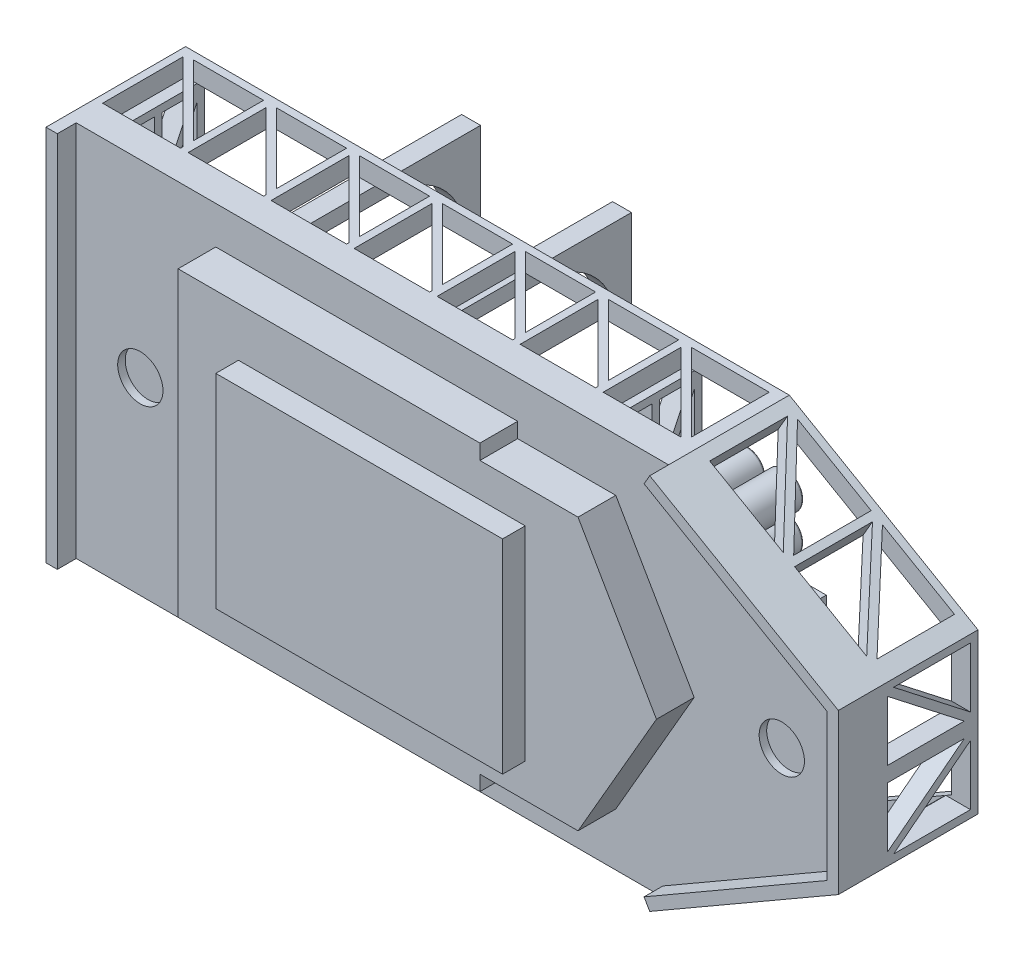
SolidWorks part; units mm, degrees
ref_plane "Front Plane" through (0, 0, 0) normal (0, 0, 1) x (1, 0, 0)
ref_plane "Top Plane" through (0, 0, 0) normal (0, 1, 0) x (1, 0, 0)
ref_plane "Right Plane" through (0, 0, 0) normal (1, 0, 0) x (0, 0, -1)
sketch "Sketch1" plane through (0, 0, 0) normal (0, 0, 1) x (1, 0, 0)
  line L0 (0, 0) -> (65, 0) construction
  line L1 (-40, -25) -> (40, -25)
  line L2 (-40, -25) -> (-40, 25)
  line L3 (-40, 25) -> (40, 25)
  line L5 (-40, -25) -> (40, 25) construction
  line L6 (-40, 25) -> (40, -25) construction
  line L7 (65, -10.5662) -> (65, 10.5662)
  line L9 (40, -25) -> (65, -10.5662)
  line L10 (40, 25) -> (65, 10.5662)
  point P0 (0, 0)
  dimension "D1" = 50
  dimension "D2" = 80
  dimension "D3" = 30
  dimension "D4" = 21.1325
extrude "Boss-Extrude1" add sketch "Sketch1" against normal blind 2
sketch "Sketch2" plane through (0, 0, -2) normal (0, 0, -1) x (-1, 0, 0)
  line L0 (40, 25) -> (40, -25) construction
  line L2 (37.5, 22.5) -> (-39.3301, 22.5)
  line L3 (-39.3301, 22.5) -> (-62.5, 9.1229)
  line L4 (-62.5, 9.1229) -> (-62.5, 0)
  line L7 (-40, 25) -> (40, 25) construction
  line L9 (-65, 10.5662) -> (-40, 25) construction
  line L10 (-65, -10.5662) -> (-65, 10.5662) construction
  line L11 (-62.5, 0) -> (-65, 0)
  line L12 (37.5, 22.5) -> (40, 22.5)
  line L13 (-65, 0) -> (-65, 10.5662)
  line L14 (40, 25) -> (40, 22.5)
  line L15 (-40, 25) -> (40, 25)
  line L16 (-65, 10.5662) -> (-40, 25)
  dimension "D2" = 2.5
  dimension "D3" = 2.5
  dimension "D4" = 2.5
extrude "Boss-Extrude2" add sketch "Sketch2" along normal blind 13
sketch "Sketch3" plane through (0, 22.5, 0) normal (0, -1, 0) x (1, 0, 0)
  line L0 (38.3301, -14) -> (28.0372, -14)
  line L1 (39.3301, -15) -> (39.3301, -2) construction
  line L2 (-40, -15) -> (-40, -2) construction
  line L3 (-39, -13.623) -> (-39, -3)
  line L4 (39.3301, -15) -> (-40, -15) construction
  line L5 (39.3301, -2) -> (-40, -2) construction
  line L6 (-39, -3) -> (-28.6699, -3)
  line L7 (38.3301, -3.7071) -> (38.3301, -14)
  line L8 (27.3301, -13.2929) -> (27.3301, -3)
  line L9 (26.3301, -14) -> (26.3301, -4.7071)
  line L10 (16.3301, -13.2929) -> (16.3301, -3)
  line L11 (15.3301, -14) -> (15.3301, -4.7071)
  line L12 (5.3301, -13.2929) -> (5.3301, -3)
  line L13 (4.3301, -14) -> (4.3301, -4.7071)
  line L14 (-5.6699, -13.2929) -> (-5.6699, -3)
  line L15 (-6.6699, -14) -> (-6.6699, -4.7071)
  line L16 (-16.6699, -13.2929) -> (-16.6699, -3)
  line L17 (-17.6699, -14) -> (-17.6699, -4.7071)
  line L18 (-27.6699, -13.2929) -> (-27.6699, -3)
  line L19 (-28.6699, -14) -> (-28.6699, -4.7071)
  line L20 (26.3301, -14) -> (17.0372, -14)
  line L21 (38.3301, -3.7071) -> (28.0372, -14)
  line L22 (37.623, -3) -> (27.3301, -13.2929)
  line L23 (26.3301, -4.7071) -> (17.0372, -14)
  line L24 (26.3301, -3.2929) -> (16.3301, -13.2929)
  line L25 (15.3301, -4.7071) -> (6.0372, -14)
  line L26 (15.3301, -3.2929) -> (5.3301, -13.2929)
  line L27 (4.3301, -4.7071) -> (-4.9628, -14)
  line L28 (4.3301, -3.2929) -> (-5.6699, -13.2929)
  line L29 (-6.6699, -4.7071) -> (-15.9628, -14)
  line L30 (-6.6699, -3.2929) -> (-16.6699, -13.2929)
  line L31 (-17.6699, -4.7071) -> (-26.9628, -14)
  line L32 (-17.6699, -3.2929) -> (-27.6699, -13.2929)
  line L33 (-28.6699, -4.7071) -> (-37.9628, -14)
  line L34 (-28.6699, -3.2929) -> (-38.6699, -13.2929)
  line L35 (-38.6699, -13.2929) -> (-39, -13.623)
  line L36 (27.3301, -3) -> (37.623, -3)
  line L37 (26.3301, -3.2929) -> (26.3301, -3)
  line L38 (15.3301, -14) -> (6.0372, -14)
  line L39 (16.3301, -3) -> (26.3301, -3)
  line L40 (15.3301, -3.2929) -> (15.3301, -3)
  line L41 (4.3301, -14) -> (-4.9628, -14)
  line L42 (5.3301, -3) -> (15.3301, -3)
  line L43 (4.3301, -3.2929) -> (4.3301, -3)
  line L44 (-6.6699, -14) -> (-15.9628, -14)
  line L45 (-5.6699, -3) -> (4.3301, -3)
  line L46 (-6.6699, -3.2929) -> (-6.6699, -3)
  line L47 (-17.6699, -14) -> (-26.9628, -14)
  line L48 (-16.6699, -3) -> (-6.6699, -3)
  line L49 (-17.6699, -3.2929) -> (-17.6699, -3)
  line L50 (-28.6699, -14) -> (-37.9628, -14)
  line L51 (-27.6699, -3) -> (-17.6699, -3)
  line L52 (-28.6699, -3.2929) -> (-28.6699, -3)
  dimension "D1" = 1
  dimension "D2" = 1
  dimension "D3" = 1
  dimension "D4" = 1
  dimension "D5" = 1
  dimension "D7" = 6
  dimension "D8" = 1
  dimension "D9" = 7
extrude "Cut-Extrude1" cut sketch "Sketch3" against normal blind 13
sketch "Sketch4" plane through (19.5753, 33.9054, 0) normal (-0.5, -0.866, 0) x (0.866, -0.5, 0)
  line L0 (23.8109, -3) -> (23.8109, -13.3217)
  line L1 (23.8109, -13.3217) -> (35.0709, -3)
  line L2 (49.5652, -15) -> (22.8109, -15) construction
  line L3 (24.5508, -14) -> (35.8109, -14)
  line L4 (22.8109, -15) -> (22.8109, -2) construction
  line L5 (49.5652, -15) -> (49.5652, -2) construction
  line L6 (48.5652, -14) -> (48.5652, -3.7301)
  line L7 (47.8334, -3) -> (36.8109, -3)
  line L8 (-22.141, -2) -> (47.141, -2) construction
  line L9 (35.8109, -3.7372) -> (35.8109, -14)
  line L10 (36.8109, -3) -> (36.8109, -13.3152)
  line L11 (35.0709, -3) -> (23.8109, -3)
  line L12 (37.5426, -14) -> (48.5652, -14)
  line L15 (24.5508, -14) -> (35.8109, -3.7372)
  line L16 (36.8109, -13.3152) -> (47.8334, -3)
  line L17 (37.5426, -14) -> (48.5652, -3.7301)
  dimension "D1" = 1
  dimension "D2" = 1
  dimension "D3" = 1
  dimension "D4" = 1
  dimension "D5" = 1
  dimension "D6" = 12
extrude "Cut-Extrude2" cut sketch "Sketch4" against normal blind 13
sketch "Sketch5" plane through (65, 0, 0) normal (1, 0, 0) x (0, 0, -1)
  line L0 (14, 9.5662) -> (3.8138, 9.5662)
  line L1 (15, 10.5662) -> (15, 0) construction
  line L3 (14, 9.5662) -> (14, 1.6337)
  line L4 (15, 10.5662) -> (0, 10.5662) construction
  line L5 (15, 0) -> (2, 0) construction
  line L6 (13.1862, 1) -> (3, 1)
  line L7 (3, 8.9325) -> (3, 1)
  line L9 (3.8138, 9.5662) -> (14, 1.6337)
  line L10 (3, 8.9325) -> (13.1862, 1)
  dimension "D1" = 1
  dimension "D2" = 1
  dimension "D3" = 1
  dimension "D4" = 1
extrude "Cut-Extrude3" cut sketch "Sketch5" against normal blind 13
mirror "Mirror1" about plane through (62.5, 0, -15) normal (0, 1, 0) of "Cut-Extrude3", "Cut-Extrude2", "Boss-Extrude2", "Cut-Extrude1"
sketch "Sketch6" plane through (0, 0, -2) normal (0, 0, -1) x (-1, 0, 0)
  line L0 (-28.4026, -22.5) -> (-28.4026, 22.5)
  line L1 (-39.3301, -22.5) -> (40, -22.5) construction
  line L2 (-39.3301, 22.5) -> (40, 22.5) construction
  line L3 (-25.9026, -22.5) -> (-25.9026, 22.5)
  line L4 (-28.4026, -22.5) -> (-25.9026, -22.5)
  line L5 (-28.4026, 22.5) -> (-25.9026, 22.5)
  dimension "D1" = 2.5
  dimension "D2" = 25.9026
extrude "Boss-Extrude3" add sketch "Sketch6" along normal blind 13
sketch "Sketch7" plane through (25.9026, 0, 0) normal (-1, 0, 0) x (0, 0, 1)
  line L0 (-14, -19.1763) -> (-14, -11.6371)
  line L1 (-8.375, -21.5) -> (-4.3039, -21.5)
  line L3 (-13.4461, 21.5) -> (-9.375, 21.5)
  line L4 (-15, -22.5) -> (-15, 22.5) construction
  line L6 (-3.75, 19.3787) -> (-3.75, 10.7886)
  line L7 (-15, 22.5) -> (-2, 22.5) construction
  line L9 (-14, -21.5) -> (-9.375, -21.5)
  line L10 (-14, -22.5) -> (-5.1346, -22.5) construction
  line L11 (-14, -11.6371) -> (-9.9702, -11.6371)
  line L12 (-2, -22.5) -> (-2, 22.5) construction
  line L15 (-8.876, 9.7886) -> (-8.875, 9.7886)
  line L19 (-14, -10.6371) -> (-9.4828, -10.6371)
  line L22 (-14, 9.7886) -> (-10.0099, 9.7886)
  line L23 (-14, 10.7886) -> (-9.4473, 10.7886)
  line L24 (-9.375, -21.5) -> (-9.375, -12.6449)
  line L25 (-8.375, -21.5) -> (-8.375, -12.9606)
  line L26 (-14.1082, -21.5) -> (-9.375, -12.6449)
  line L27 (-14, -19.1763) -> (-9.9702, -11.6371)
  line L28 (-14, 20.3381) -> (-9.4473, 10.7886)
  line L29 (-13.4461, 21.5) -> (-9.375, 12.9606)
  line L30 (-4.3039, -21.5) -> (-8.375, -12.9606)
  line L31 (-3.75, -20.3381) -> (-7.8982, -11.6371)
  line L32 (-3.75, 19.3787) -> (-8.3415, 10.7886)
  line L33 (-3.75, 21.5) -> (-8.375, 12.8473)
  line L37 (-14, -10.6371) -> (-14, -1.1619)
  line L38 (-3.75, -11.6371) -> (-3.75, -20.3381)
  line L39 (-8.3018, -10.6371) -> (-3.75, -2.1213)
  line L40 (-8.3018, -10.6371) -> (-3.75, -10.6371)
  line L41 (-3.75, -2.1213) -> (-3.75, -10.6371)
  line L43 (-9.4828, -10.6371) -> (-14, -1.1619)
  line L45 (-9.375, -8.5394) -> (-9.375, -0.5)
  line L46 (-9.375, -8.5394) -> (-13.2077, -0.5)
  line L47 (-8.375, -8.6527) -> (-4.0173, -0.5)
  line L48 (-8.375, -8.6527) -> (-8.375, -0.5)
  line L50 (-8.375, -0.5) -> (-4.0173, -0.5)
  line L51 (-8.375, 0.5) -> (-8.375, 8.5394)
  line L52 (-9.375, 0.5) -> (-9.375, 8.8551)
  line L53 (-13.2077, -0.5) -> (-9.375, -0.5)
  line L56 (-8.375, 0.5) -> (-4.5423, 0.5)
  line L57 (-13.8409, 0.5) -> (-9.375, 0.5)
  line L58 (-14, 2.3237) -> (-14, 9.7886)
  line L59 (-8.375, 8.5394) -> (-4.5423, 0.5)
  line L61 (-7.8627, 9.7886) -> (-3.75, 9.7886)
  line L62 (-7.8627, 9.7886) -> (-3.75, 1.1619)
  line L63 (-9.375, 8.8551) -> (-13.8409, 0.5)
  line L66 (-10.0099, 9.7886) -> (-14, 2.3237)
  line L67 (-14, 10.7886) -> (-14, 20.3381)
  line L68 (-3.75, 9.7886) -> (-3.75, 1.1619)
  line L69 (-9.375, 12.9606) -> (-9.375, 21.5)
  line L72 (-8.375, 12.8473) -> (-8.375, 21.5)
  line L73 (-8.375, 21.5) -> (-3.75, 21.5)
  line L78 (-8.3415, 10.7886) -> (-3.75, 10.7886)
  line L79 (-7.8982, -11.6371) -> (-3.75, -11.6371)
  line L81 (-8.375, -10.6371) -> (-8.375, -10.6369)
  line L83 (-14.1082, -21.5) -> (-14, -21.5)
  line L86 (-8.875, 9.7886) -> (-8.875, 9.7905) construction
  dimension "D1" = 1
  dimension "D2" = 1
  dimension "D3" = 1
  dimension "D4" = 1.75
  dimension "D5" = 1
  dimension "D6" = 1
  dimension "D7" = 1
  dimension "D9" = 1
  dimension "D10" = 1
  dimension "D11" = 1
  dimension "D12" = 1
extrude "Cut-Extrude4" cut sketch "Sketch7" against normal blind 6 contours L26 L83 L9 L24 | L0 L27 L11 | L19 L43 L37 | L53 L46 L45 | L50 L48 L47 | L59 L51 L56 | L52 L63 L57 | L67 L23 L28 | L29 L69 L3 | L73 L72 L33 | L32 L78 L6 | L68 L61 L62 | L41 L39 L40 | L79 L31 L38 | L1 L30 L25 | L58 L22 L66 region at (25.9026, -14.1501, -12.6567) region at (25.9026, -18.6535, -7.018) region at (25.9026, 18.6535, -10.732) region at (25.9026, 13.6519, -5.2805) region at (25.9026, -18.5483, -10.9527) region at (25.9026, -7.4787, -12.4943) region at (25.9026, 13.9718, -12.4824) region at (25.9026, -14.5374, -5.1327) region at (25.9026, 18.6158, -6.8333) region at (25.9026, -7.7985, -5.2673) region at (25.9026, -3.1798, -10.6526) region at (25.9026, -3.2176, -6.9224) region at (25.9026, 3.1798, -7.0974) region at (25.9026, 3.285, -10.8636) region at (25.9026, 6.913, -5.1209)
ref_plane "Plane1" through (-5.7974, 0, 0) normal (1, 0, 0) x (0, 0, -1)
mirror "Mirror2" about plane through (-5.7974, 0, 0) normal (1, 0, 0) of "Cut-Extrude4", "Boss-Extrude3"
sketch "Sketch8" plane through (-39.9974, 0, 0) normal (-1, 0, 0) x (0, 0, 1)
  line L0 (-15, -10.6371) -> (-2, -10.6371)
  line L1 (-15, 22.5) -> (-15, -22.5) construction
  line L2 (-2, 22.5) -> (-2, -22.5) construction
  line L3 (-2, -10.6371) -> (-2, 9.7886)
  line L4 (-2, 9.7886) -> (-15, 9.7886)
  line L5 (-15, 9.7886) -> (-15, -10.6371)
extrude "Cut-Extrude5" cut sketch "Sketch8" against normal blind 6
sketch "Sketch9" plane through (0, 0, -2) normal (0, 0, -1) x (-1, 0, 0)
  line L0 (-6.0795, 22.5) -> (-6.0795, 7.5)
  line L1 (-25.9026, 22.5) -> (37.4974, 22.5) construction
  line L2 (-6.0795, 7.5) -> (-3.5795, 7.5)
  line L3 (-3.5795, 7.5) -> (-3.5795, 22.5)
  line L4 (-6.0795, 22.5) -> (-3.5795, 22.5)
  dimension "D1" = 2.5
  dimension "D2" = 3.5795
  dimension "D3" = 15
extrude "Boss-Extrude4" add sketch "Sketch9" along normal blind 26
sketch "Sketch11" plane through (0, 0, 0) normal (0, 0, 1) x (1, 0, 0)
  line L7 (-40, -25) -> (40, -25)
  line L8 (40, -25) -> (65, -10.5662)
  line L9 (65, -10.5662) -> (65, 10.5662)
  line L10 (65, 10.5662) -> (40, 25)
  line L11 (40, 25) -> (-40, 25)
  line L12 (-40, 25) -> (-40, -25)
  line L13 (-40, -25) -> (40, -25)
  line L14 (40, -25) -> (65, -10.5662)
  line L15 (65, -10.5662) -> (65, 10.5662)
  line L16 (65, 10.5662) -> (40, 25)
  line L17 (40, 25) -> (-40, 25)
  line L18 (-40, 25) -> (-40, -25)
  circle A0 centre (55, 0) radius 3
  circle A1 centre (-30, 0) radius 3
  dimension "D1" = 6
  dimension "D2" = 55
  dimension "D3" = 30
  dimension "D4" = 0
extrude "Boss-Extrude6" add sketch "Sketch11" along normal blind 1
sketch "Sketch12" plane through (0, 0, 1) normal (0, 0, 1) x (1, 0, 0)
  line L1 (-20, -20) -> (20, -20)
  line L2 (-20, -20) -> (-20, 20)
  line L3 (-20, 20) -> (20, 20)
  line L4 (20, -20) -> (20, 20)
  line L5 (-20, -20) -> (20, 20) construction
  line L6 (-20, 20) -> (20, -20) construction
  point P0 (0, 0)
  dimension "D1" = 40
  dimension "D2" = 20
extrude "Boss-Extrude7" add sketch "Sketch12" along normal blind 5
sketch "Sketch13" plane through (0, 0, 1) normal (0, 0, 1) x (1, 0, 0)
  line L0 (20, 0) -> (43.7696, 0) construction
  line L1 (20, -20) -> (20, 20) construction
  line L2 (20, 18) -> (33, 18)
  line L3 (33, 18) -> (43.3923, 0)
  line L4 (33, -18) -> (43.3923, 0)
  line L5 (20, -18) -> (33, -18)
  line L6 (20, 18) -> (20, -18)
  dimension "D1" = 60
  dimension "D2" = 13
  dimension "D3" = 18
extrude "Boss-Extrude8" add sketch "Sketch13" along normal blind 5
sketch "Sketch14" plane through (0, 0, 6) normal (0, 0, 1) x (1, 0, 0)
  line L1 (-12, -13.4999) -> (26, -13.4999)
  line L2 (-12, -13.4999) -> (-12, 13.4999)
  line L3 (-12, 13.4999) -> (26, 13.4999)
  line L4 (26, -13.4999) -> (26, 13.4999)
  line L5 (-12, -13.4999) -> (26, 13.4999) construction
  line L6 (-12, 13.4999) -> (26, -13.4999) construction
  point P0 (7, 0)
  dimension "D1" = 7
  dimension "D2" = 26.9999
  dimension "D3" = 38
extrude "Boss-Extrude9" add sketch "Sketch14" along normal blind 3
sketch "Sketch15" plane through (0, 0, 1) normal (0, 0, 1) x (1, 0, 0)
  line L0 (-40, 25) -> (-40, -25) construction
  line L1 (40, -25) -> (65, -10.5662) construction
  line L2 (65, -10.5662) -> (65, 10.5662) construction
  line L3 (65, 10.5662) -> (40, 25) construction
  line L4 (-40, 25) -> (-40, -25)
  line L5 (40, -25) -> (65, -10.5662)
  line L6 (65, -10.5662) -> (65, 10.5662)
  line L7 (65, 10.5662) -> (40, 25)
  line L8 (-38.5, 25) -> (-38.5, -25)
  line L9 (39.25, -23.701) -> (63.5, -9.7002)
  line L10 (63.5, -9.7002) -> (63.5, 9.7002)
  line L11 (63.5, 9.7002) -> (39.25, 23.701)
  line L12 (-40, 25) -> (-38.5, 25)
  line L13 (-40, -25) -> (-38.5, -25)
  line L14 (39.25, -23.701) -> (40, -25)
  line L15 (40, 25) -> (39.25, 23.701)
  dimension "D1" = 1.5
extrude "Boss-Extrude10" add sketch "Sketch15" along normal blind 2.5
sketch "Sketch16" plane through (3.5795, 0, 0) normal (-1, 0, 0) x (0, 0, 1)
  line L0 (-2, 7.5) -> (-26, 7.5)
  line L1 (-28, 7.5) -> (-2, 7.5) construction
  line L3 (-16, 20.5) -> (-2, 20.5)
  line L4 (-2, 22.5) -> (-2, 9.7886) construction
  line L5 (-2, 20.5) -> (-2, 7.5)
  line L7 (-26, 10.5) -> (-28, 10.5)
  line L8 (-28, 7.5) -> (-28, 22.5) construction
  line L9 (-28, 10.5) -> (-28, 7.5)
  line L10 (-28, 7.5) -> (-26, 7.5)
  arc A0 (-26, 10.5) -> (-16, 20.5) centre (-16, 10.5) cw
  point P13 (-26, 20.5)
  dimension "D3" = 10
  dimension "D1" = 24
  dimension "D2" = 13
extrude "Cut-Extrude6" cut sketch "Sketch16" against normal blind 5
pattern_linear "LPattern1" count 2 spacing 20 along (-1, 0, 0) of "Cut-Extrude6", "Boss-Extrude4"
mirror "Mirror3" about plane through (0, 0, 0) normal (0, 1, 0) of "Boss-Extrude4", "LPattern1", "Cut-Extrude6"
sketch "Sketch17" plane through (0, 0, -2) normal (0, 0, -1) x (-1, 0, 0)
  line L0 (6.1995, 0) -> (-74.6011, 0) construction
  line L2 (-50.4, -10) -> (-40.6, -10)
  line L4 (-50.4, 10) -> (-40.6, 10)
  line L6 (-50.5, -10) -> (-40.5, 10) construction
  line L7 (-50.5, 10) -> (-40.5, -10) construction
  line L12 (-41, 10) -> (-41, 15.5)
  line L13 (-41, 15.5) -> (-30, 15.5)
  line L14 (-30, 15.5) -> (-30, -15.5)
  line L15 (-30, -15.5) -> (-41, -15.5)
  line L16 (-41, -15.5) -> (-41, -10)
  line L18 (-35.5, 15) -> (-35.5, -15) construction
  line L19 (-40.5, 10) -> (-40.6, 10)
  line L20 (-50.4, -9.9) -> (-50.4, 9.9)
  line L21 (-40.6, 10) -> (-40.6, -10)
  line L22 (-50.4, 9.9) -> (-50.4, 10)
  line L23 (-50.4, 9.9) -> (-40.5, 9.9) construction
  line L24 (-50.4, -9.9) -> (-50.4, -10)
  line L25 (-50.4, -9.9) -> (-40.5, -9.9) construction
  line L26 (-50.5, -10) -> (-50.5, 10) construction
  line L27 (-50.5, -10) -> (-40.5, -10) construction
  line L28 (-50.5, 10) -> (-40.5, 10) construction
  line L29 (-40.5, -10) -> (-40.6, -10)
  line L30 (-40.6, 10.1) -> (-40.6, 10.1)
  line L31 (-40.6, 10.1) -> (-40.6, 15.1)
  line L32 (-40.6, 15.1) -> (-30.4, 15.1)
  line L33 (-30.4, 15.1) -> (-30.4, -15.1)
  line L34 (-30.4, -15.1) -> (-40.6, -15.1)
  line L35 (-40.6, -15.1) -> (-40.6, -10.1)
  line L36 (-40.6, -10.1) -> (-40.6, -10.1)
  line L37 (-40.5, -15) -> (-40.5, -10) construction
  line L38 (-30.5, -15) -> (-40.5, -15) construction
  line L39 (-40.6, -10.1) -> (-40.6, -10)
  line L40 (-40.6, 10.1) -> (-40.6, 10)
  line L42 (-40.5, 10) -> (-40.5, 15) construction
  line L43 (-40.5, 15) -> (-30.5, 15) construction
  line L44 (-30.5, 15) -> (-30.5, -15) construction
  circle A0 centre (-55, 0) radius 4.5
  circle A13 centre (-33, 12.5) radius 2.4
  circle A14 centre (-33, 7.5) radius 2.4
  circle A15 centre (-33, 2.5) radius 2.4
  circle A16 centre (-33, -2.5) radius 2.4
  circle A17 centre (-33, -7.5) radius 2.4
  circle A18 centre (-33, -12.5) radius 2.4
  circle A20 centre (-38, 12.5) radius 2.4
  circle A21 centre (-38, 7.5) radius 2.4
  circle A22 centre (-38, 2.5) radius 2.4
  circle A23 centre (-38, -2.5) radius 2.4
  circle A24 centre (-38, -7.5) radius 2.4
  circle A25 centre (-38, -12.5) radius 2.4
  point P5 (-45.5, 0)
  dimension "D1" = 9
  dimension "D2" = 20
  dimension "D3" = 10
  dimension "D12" = 0.1
  dimension "D11" = 0.1
extrude "Boss-Extrude11" add sketch "Sketch17" along normal blind 5 contours A0 region at (55, 0, -2)
extrude "Boss-Extrude14" add sketch "Sketch17<4>" along normal blind 7.5 contours L20 L24 L2 L21 L4 L22 region at (45.5, 0, -2)
sketch "Sketch17<4>" plane through (0, 0, -2) normal (0, 0, -1) x (-1, 0, 0) same geometry as "Sketch17"
extrude "Boss-Extrude15" add sketch "Sketch17<5>" along normal blind 4.5 contours L40 L31 L32 L33 L34 L35 L39 L2 L16 L15 L14 L13 L12 L4 region at (40.8, -10.3289, -2)
sketch "Sketch17<5>" plane through (0, 0, -2) normal (0, 0, -1) x (-1, 0, 0) same geometry as "Sketch17"
extrude "Boss-Extrude19" add sketch "Sketch17<8>" along normal blind 14.5 contours A20 | A13 | A21 | A14 | A22 | A15 | A23 | A16 | A24 | A17 | A25 | A18 region at (33, 12.5, -2) region at (33, 7.5, -2) region at (33, 2.5, -2) region at (33, -2.5, -2) region at (33, -7.5, -2) region at (33, -12.5, -2) region at (38, 12.5, -2) region at (38, 7.5, -2) region at (38, 2.5, -2) region at (38, -2.5, -2) region at (38, -7.5, -2) region at (38, -12.5, -2)
sketch "Sketch17<8>" plane through (0, 0, -2) normal (0, 0, -1) x (-1, 0, 0) same geometry as "Sketch17"
fillet "Fillet3" radius 0.25 12 edges at (30.6, -12.5, -16.5) (30.6, -7.5, -16.5) (30.6, -2.5, -16.5) (30.6, 2.5, -16.5) (30.6, 7.5, -16.5) (30.6, 12.5, -16.5) (35.6, -12.5, -16.5) (35.6, -7.5, -16.5) (35.6, -2.5, -16.5) (35.6, 2.5, -16.5) (35.6, 7.5, -16.5) (35.6, 12.5, -16.5)
fillet "Fillet4" radius 0.5 1 edges at (50.5, 0, -7)
